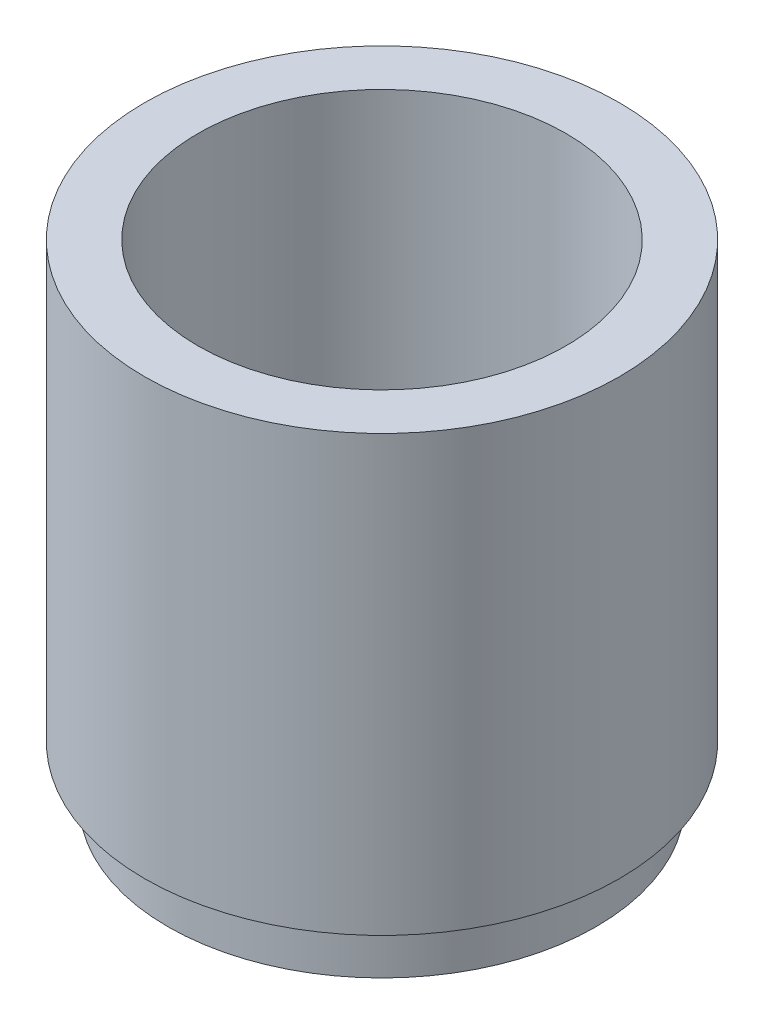
SolidWorks part; units mm, degrees
ref_plane "Front Plane" through (0, 0, 0) normal (0, 0, 1) x (1, 0, 0)
ref_plane "Top Plane" through (0, 0, 0) normal (0, 1, 0) x (1, 0, 0)
ref_plane "Right Plane" through (0, 0, 0) normal (1, 0, 0) x (0, 0, -1)
sketch "Sketch1" plane through (0, 0, 0) normal (0, 1, 0) x (1, 0, 0)
  circle A0 centre (0, 0) radius 8.025
  circle A1 centre (0, 0) radius 6.4
  dimension "D1" = 16.05
  dimension "D2" = 12.8
extrude "Boss-Extrude1" add sketch "Sketch1" along normal blind 2
sketch "Sketch2" plane through (0, 2, 0) normal (0, 1, 0) x (1, 0, 0)
  circle A0 centre (0, 0) radius 8.9
  circle A1 centre (0, 0) radius 6.9
  dimension "D1" = 17.8
  dimension "D2" = 13.8
extrude "Boss-Extrude2" add sketch "Sketch2" along normal blind 16.3
